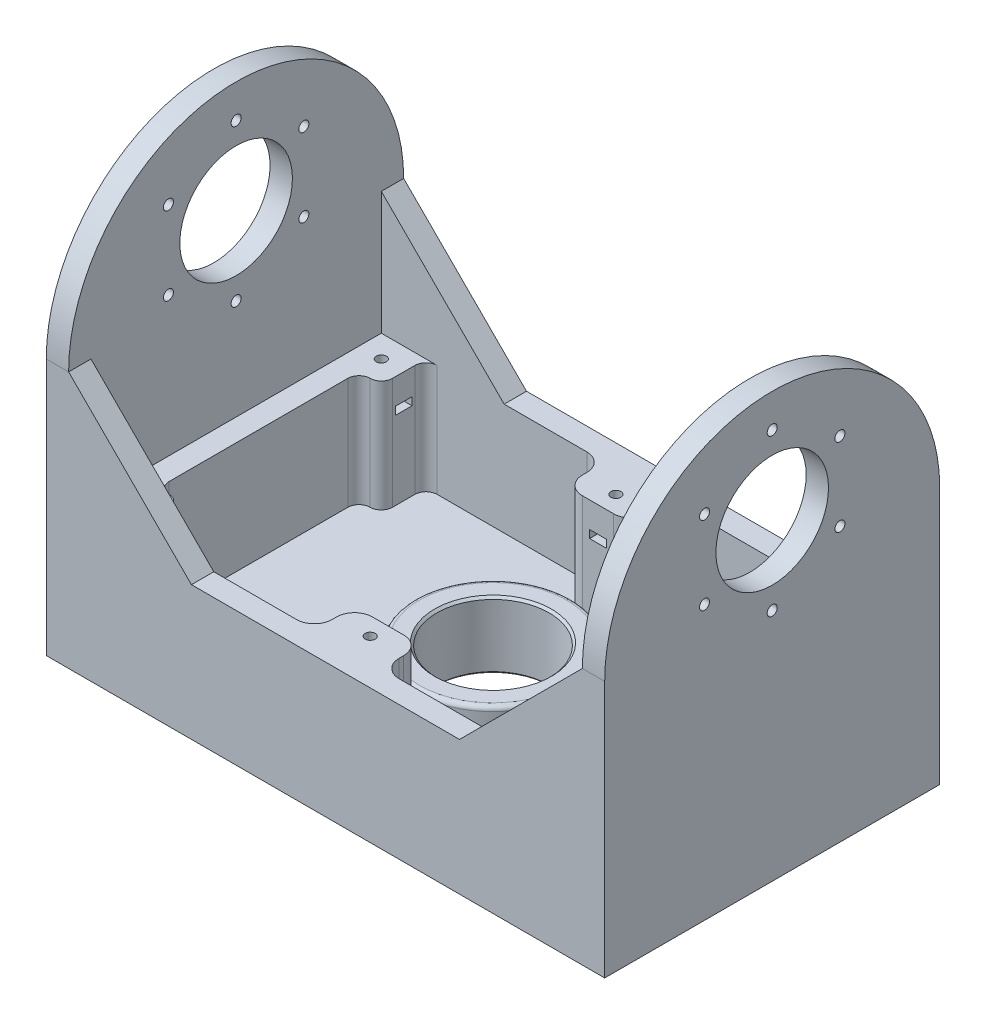
SolidWorks part; units mm, degrees
ref_plane "Front Plane" through (0, 0, 0) normal (0, 0, 1) x (1, 0, 0)
ref_plane "Top Plane" through (0, 0, 0) normal (0, 1, 0) x (1, 0, 0)
ref_plane "Right Plane" through (0, 0, 0) normal (1, 0, 0) x (0, 0, -1)
sketch "Sketch3" plane through (0, 0, 0) normal (0, 1, 0) x (1, 0, 0)
  line L0 (0, -93.3232) -> (0, 91.047) construction
  line L1 (-147.1927, 0) -> (149.8483, 0) construction
  line L3 (-125, -75) -> (125, -75)
  line L4 (-125, -75) -> (-125, 75)
  line L5 (-125, 75) -> (125, 75)
  line L6 (125, -75) -> (125, 75)
  line L7 (-125, -75) -> (125, 75) construction
  line L8 (-125, 75) -> (125, -75) construction
  point P5 (0, 0)
  dimension "D1" = 250
  dimension "D2" = 150
extrude "Boss-Extrude1" add sketch "Sketch3" along normal blind 10
ref_axis "Axis1" through (0, 0, 0) along (0, 1, 0)
sketch "Sketch4" plane through (0, 10, 0) normal (0, 1, 0) x (1, 0, 0)
  circle A0 centre (0, 0) radius 35
  dimension "D1" = 70
extrude "Boss-Extrude2" add sketch "Sketch4" along normal blind 20
sketch "Sketch5" plane through (0, 30, 0) normal (0, 1, 0) x (1, 0, 0)
  circle A0 centre (0, 0) radius 25.15
  dimension "D1" = 50.3
extrude "Cut-Extrude1" cut sketch "Sketch5" against normal through all
chamfer "Chamfer1" distance 1 angle 45 2 edges at (0, 0, 25.15) (0, 30, 25.15)
fillet "Fillet1" radius 2 1 edges at (0, 30, 35)
fillet "Fillet2" radius 10 1 edges at (0, 10, 35)
sketch "Sketch8" plane through (-125, 0, 0) normal (-1, 0, 0) x (0, 0, 1)
  line L0 (-75, 10) -> (-75, 115)
  line L1 (0, 0) -> (0, 254.622) construction
  line L2 (0, 0) -> (0, 96.2107) construction
  line L4 (75, 10) -> (75, 115)
  line L5 (-75, 10) -> (75, 10)
  arc A0 (-75, 115) -> (75, 115) centre (0, 115) cw
  dimension "D2" = 75
extrude "Boss-Extrude3" add sketch "Sketch8" against normal blind 10
mirror "Mirror1" about plane through (0, 0, 0) normal (1, 0, 0) of "Boss-Extrude3"
sketch "Sketch9" plane through (0, 10, 0) normal (0, 1, 0) x (1, 0, 0)
  line L0 (-115, -75) -> (115, -75) construction
  line L1 (115, 75) -> (115, -75) construction
  line L2 (115, 75) -> (-115, 75) construction
  line L3 (-115, -75) -> (-115, 75) construction
  line L4 (-115, -75) -> (115, -75)
  line L5 (115, 75) -> (115, -75)
  line L6 (115, 75) -> (-115, 75)
  line L7 (-115, -75) -> (-115, 75)
  line L8 (105, 65) -> (-105, 65)
  line L9 (-105, -65) -> (-105, 65)
  line L10 (-105, -65) -> (105, -65)
  line L11 (105, 65) -> (105, -65)
  dimension "D1" = 10
extrude "Boss-Extrude4" add sketch "Sketch9" along normal blind 50
sketch "Sketch10" plane through (0, 0, 75) normal (0, 0, 1) x (1, 0, 0)
  line L0 (-115, 115) -> (-60, 60)
  line L1 (-115, 60) -> (115, 60) construction
  line L2 (-60, 60) -> (-115, 60)
  line L3 (-115, 60) -> (-115, 115)
extrude "Boss-Extrude5" add sketch "Sketch10" against normal blind 10
sketch "Sketch11" plane through (0, 10, 0) normal (0, 1, 0) x (1, 0, 0)
  line L0 (-115, -75) -> (-115, 75) construction
  line L6 (-60, -65) -> (-115, -65) construction
  line L7 (-105, -65) -> (-95, -65)
  line L8 (-105, -65) -> (-105, -45)
  line L9 (-105, -45) -> (-95, -45)
  line L10 (-95, -65) -> (-95, -45)
  dimension "D3" = 20
  dimension "D4" = 20
extrude "Boss-Extrude7" add sketch "Sketch11" along normal up to surface (50 mm away) up to face at (-12, 60, 13)
sketch "Sketch13" plane through (0, 60, 0) normal (0, 1, 0) x (1, 0, 0)
  circle A0 centre (-105, -55) radius 2.25
  dimension "D1" = 4.5
extrude "Cut-Extrude2" cut sketch "Sketch13" against normal blind 25
ref_plane "Plane2" through (0, 45, 0) normal (0, 1, 0) x (1, 0, 0)
sketch "Sketch14" plane through (0, 45, 0) normal (0, 1, 0) x (1, 0, 0)
  line L0 (-105, -55) -> (-95, -55) construction
  line L1 (-95, -65) -> (-95, -45) construction
  line L2 (-102.8349, -51.25) -> (-95, -51.25)
  line L4 (-102.8349, -51.25) -> (-107.1651, -51.25)
  line L5 (-107.1651, -51.25) -> (-109.3301, -55)
  line L6 (-109.3301, -55) -> (-107.1651, -58.75)
  line L7 (-107.1651, -58.75) -> (-102.8349, -58.75)
  line L9 (-95, -51.25) -> (-95, -58.75)
  line L10 (-95, -65) -> (-95, -45) construction
  line L11 (-95, -58.75) -> (-102.8349, -58.75)
  line L13 (-101.7524, -53.125) -> (-102.8349, -51.25) [skipped]
  line L14 (-102.8349, -58.75) -> (-101.7524, -56.875) [skipped]
  circle A0 centre (-105, -55) radius 3.75 construction
  dimension "D1" = 7.5
extrude "Cut-Extrude3" cut sketch "Sketch14" along normal blind 3.5
fillet "Fillet3" radius 5 3 edges at (-95, 35, 65) (-105, 35, 45) (-95, 35, 45)
mirror "Mirror2" about plane through (0, 0, 0) normal (0, 0, 1) of "Cut-Extrude3", "Cut-Extrude2", "Boss-Extrude7", "Boss-Extrude5"
mirror "Mirror3" about plane through (0, 0, 0) normal (1, 0, 0) of "Mirror2"
fillet "Fillet4" radius 5 9 edges at (95, 35, 65) (95, 35, 45) (105, 35, 45) (105, 35, -45) (95, 35, -45) (95, 35, -65) (-95, 35, -65) (-95, 35, -45) (-105, 35, -45)
sketch "Sketch15" plane through (0, 10, 0) normal (0, 1, 0) x (1, 0, 0)
  line L0 (0, 65) -> (0, -65) construction
  line L1 (60, 65) -> (-60, 65) construction
  line L2 (-60, -65) -> (60, -65) construction
  line L3 (-15, -65) -> (-15, -47)
  line L4 (-15, -47) -> (15, -47)
  line L5 (15, -65) -> (15, -47)
  line L6 (-15, -65) -> (15, -65)
  point P10 (0, -47)
  dimension "D1" = 30
  dimension "D2" = 18
extrude "Boss-Extrude8" add sketch "Sketch15" along normal up to surface (50 mm away) up to face at (-105, 60, -57.25)
sketch "Sketch17" plane through (0, 60, 0) normal (0, 1, 0) x (1, 0, 0)
  line L0 (-105, -55) -> (105, -55) construction
  circle A0 centre (0, -55) radius 2.25
  dimension "D1" = 4.5
extrude "Cut-Extrude4" cut sketch "Sketch17" against normal blind 25
sketch "Sketch18" plane through (0, 45, 0) normal (0, 1, 0) x (1, 0, 0)
  line L0 (-3.75, -52.8349) -> (-3.75, -47)
  line L1 (0, -59.3301) -> (3.75, -57.1651)
  line L2 (3.75, -57.1651) -> (3.75, -52.8349)
  line L5 (-3.75, -52.8349) -> (-3.75, -57.1651)
  line L6 (-3.75, -57.1651) -> (0, -59.3301)
  line L7 (15, -47) -> (-15, -47) construction
  line L8 (3.75, -52.8349) -> (3.75, -47)
  line L9 (-3.75, -47) -> (3.75, -47)
  line L10 (0, -50.6699) -> (-1.875, -51.7524) [skipped]
  line L11 (3.75, -52.8349) -> (1.875, -51.7524) [skipped]
  circle A0 centre (0, -55) radius 3.75 construction
  dimension "D1" = 7.5
extrude "Cut-Extrude5" cut sketch "Sketch18" along normal blind 3.5
fillet "Fillet5" radius 8 4 edges at (-15, 35, 65) (15, 35, 65) (15, 35, 47) (-15, 35, 47)
mirror "Mirror4" about plane through (0, 0, 0) normal (0, 0, 1) of "Cut-Extrude4", "Boss-Extrude8", "Cut-Extrude5"
fillet "Fillet6" radius 8 4 edges at (15, 35, -65) (15, 35, -47) (-15, 35, -65) (-15, 35, -47)
sketch "Sketch19" plane through (125, 0, 0) normal (1, 0, 0) x (0, 0, -1)
  line L0 (0, 190) -> (0, 103.1193) construction
  line L1 (-75, 0) -> (75, 0) construction
  arc A0 (75, 115) -> (-75, 115) centre (0, 115) ccw construction
  circle A1 centre (0, 140) radius 25.2
  dimension "D2" = 50.4
  dimension "D1" = 140
extrude "Cut-Extrude6" cut sketch "Sketch19" against normal up to next
sketch "Sketch20" plane through (125, 0, 0) normal (1, 0, 0) x (0, 0, -1)
  line L0 (0, 140) -> (0, 100.9701) construction
  circle A0 centre (0, 105) radius 2.25
  dimension "D1" = 4.5
  dimension "D2" = 35
extrude "Cut-Extrude7" cut sketch "Sketch20" against normal up to next
pattern_circular "CirPattern1" count 6 over 360 about axis through (-125.001, 140, 0) along (1, 0, 0) of "Cut-Extrude7"
mirror "Mirror5" about plane through (0, 0, 0) normal (1, 0, 0) of "Cut-Extrude6", "CirPattern1"
sketch "Sketch21" plane through (115, 0, 0) normal (-1, 0, 0) x (0, 0, 1)
  line L1 (0, 170.6699) -> (3.75, 172.8349)
  line L2 (3.75, 172.8349) -> (3.75, 177.1651)
  line L3 (3.75, 177.1651) -> (0, 179.3301)
  line L4 (0, 179.3301) -> (-3.75, 177.1651)
  line L5 (-3.75, 177.1651) -> (-3.75, 172.8349)
  line L6 (-3.75, 172.8349) -> (0, 170.6699)
  circle A0 centre (0, 175) radius 3.75 construction
  dimension "D1" = 7.5
extrude "Cut-Extrude8" cut sketch "Sketch21" against normal blind 3.5
pattern_circular "CirPattern2" count 6 over 360 about axis through (-125.001, 140, 0) along (1, 0, 0) of "Cut-Extrude8"
